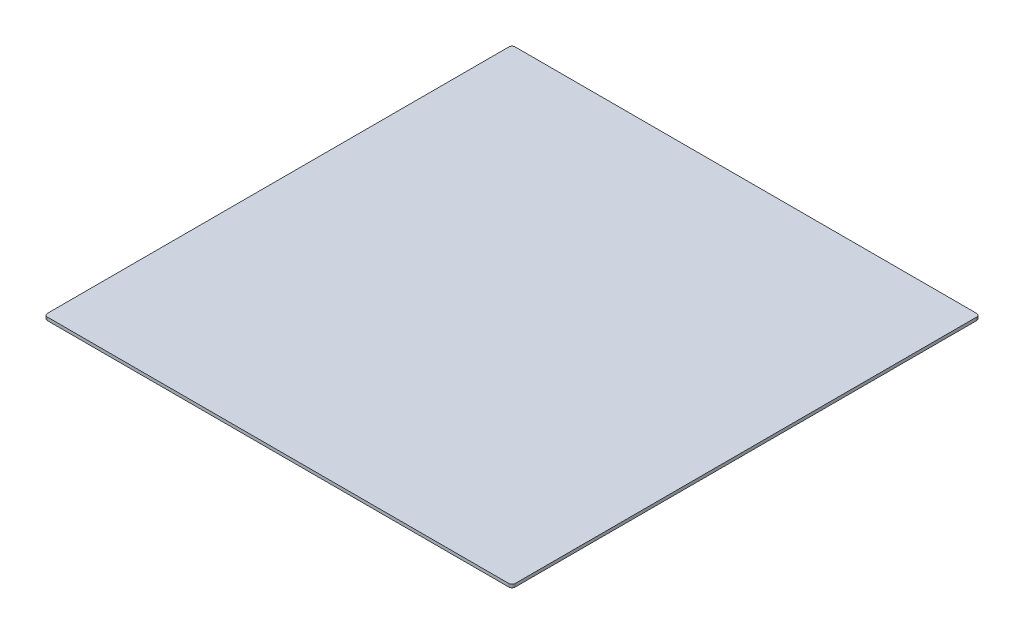
SolidWorks part; units mm, degrees
ref_plane "Front Plane" through (0, 0, 0) normal (0, 0, 1) x (1, 0, 0)
ref_plane "Top Plane" through (0, 0, 0) normal (0, 1, 0) x (1, 0, 0)
ref_plane "Right Plane" through (0, 0, 0) normal (1, 0, 0) x (0, 0, -1)
sketch "Sketch1" plane through (0, 0, 0) normal (0, 1, 0) x (1, 0, 0)
  line L1 (-150, -150) -> (150, -150)
  line L2 (-150, -150) -> (-150, 150)
  line L3 (-150, 150) -> (150, 150)
  line L4 (150, -150) -> (150, 150)
  line L5 (-150, -150) -> (150, 150) construction
  line L6 (-150, 150) -> (150, -150) construction
  point P0 (0, 0)
  dimension "D1" = 300
  dimension "D2" = 300
extrude "Boss-Extrude1" add sketch "Sketch1" along normal blind 1 and the other way blind 1
fillet "Fillet1" radius 2 4 edges at (-150, 0, -150) (150, 0, -150) (150, 0, 150) (-150, 0, 150)
